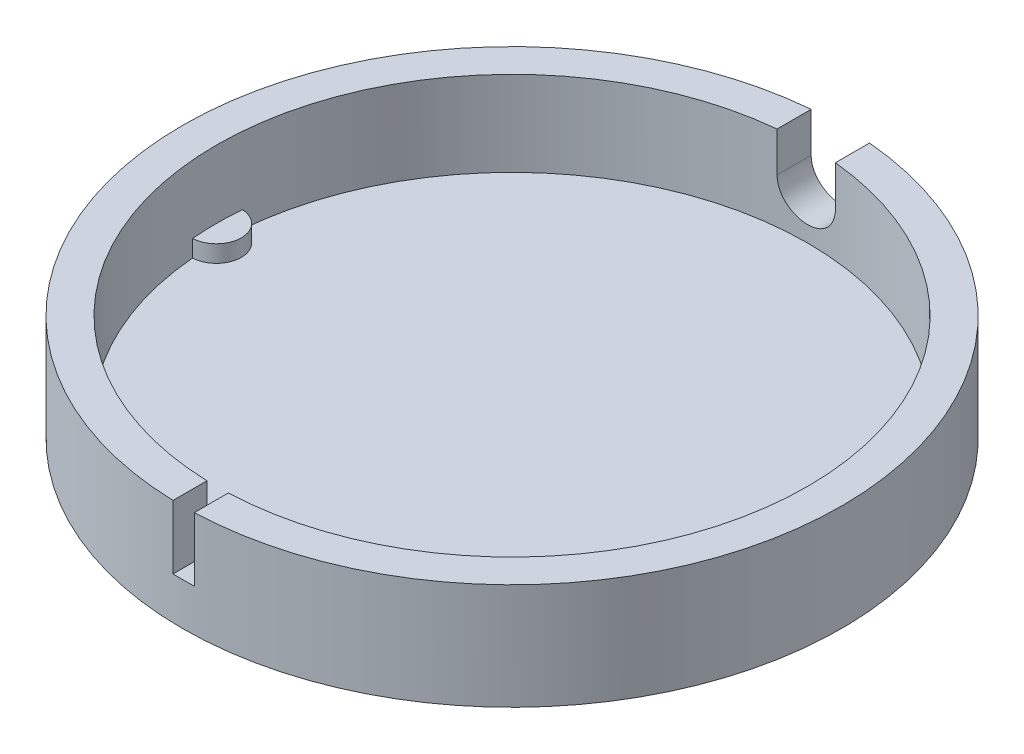
SolidWorks part; units mm, degrees
ref_plane "Front Plane" through (0, 0, 0) normal (0, 0, 1) x (1, 0, 0)
ref_plane "Top Plane" through (0, 0, 0) normal (0, 1, 0) x (1, 0, 0)
ref_plane "Right Plane" through (0, 0, 0) normal (1, 0, 0) x (0, 0, -1)
sketch "Sketch1" plane through (0, 0, 0) normal (0, 1, 0) x (1, 0, 0)
  circle A0 centre (0, 0) radius 31.06
  dimension "D1" = 62.12
extrude "Boss-Extrude1" add sketch "Sketch1" along normal blind 10
sketch "Sketch2" plane through (0, 10, 0) normal (0, 1, 0) x (1, 0, 0)
  circle A0 centre (0, 0) radius 27.86
  circle A1 centre (0, 0) radius 31.06 construction
  circle A2 centre (0, 0) radius 31.06
  dimension "D1" = 3.2
extrude "Cut-Extrude1" cut sketch "Sketch2" against normal blind 8 contours A0 region at (0, 10, 0)
sketch "Sketch3" plane through (0, 2, 0) normal (0, 1, 0) x (1, 0, 0)
  arc A0 (-27.7609, -2.3479) -> (-27.7609, 2.3479) centre (-27.86, 0) ccw
  circle A1 centre (0, 0) radius 27.86 construction
  arc A2 (27.7609, 2.3479) -> (27.7609, -2.3479) centre (27.86, 0) ccw
  arc A3 (27.7609, -2.3479) -> (27.7609, 2.3479) centre (0, 0) ccw
  arc A4 (-27.7609, 2.3479) -> (-27.7609, -2.3479) centre (0, 0) ccw
  dimension "D1" = 4.7
  dimension "D2" = 4.7
extrude "Boss-Extrude2" add sketch "Sketch3" along normal blind 1.6
sketch "Sketch4" plane through (0, 0, 0) normal (0, 0, 1) x (1, 0, 0)
  line L0 (27.7609, 2) -> (-27.7609, 2) construction
  line L1 (27.7609, 2) -> (-27.7609, 2)
  line L2 (0, 0) -> (0, 4.7714)
  line L3 (27.86, 10) -> (-27.86, 10) construction
  line L4 (27.86, 10) -> (-27.86, 10)
  line L5 (-2.75, 6.25) -> (-2.75, 10)
  line L6 (2.75, 6.25) -> (2.75, 10)
  circle A0 centre (0, 6.25) radius 2.75
  dimension "D1" = 5.5
  dimension "D2" = 4.25
extrude "Cut-Extrude2" cut sketch "Sketch4" against normal through all contours A0 L6 L4 L5 | A0 region at (0, 9.0865, 0)
sketch "Sketch5" plane through (0, 0, 0) normal (0, 0, 1) x (1, 0, 0)
  line L0 (27.86, 10) -> (-27.86, 10) construction
  line L1 (1.0982, 3.999) -> (-0.9018, 3.999)
  line L2 (1.0982, 3.999) -> (1.0982, 10)
  line L3 (1.0982, 5.999) -> (-0.9018, 5.999)
  line L4 (-0.9018, 3.999) -> (-0.9018, 10)
  line L5 (1.0982, 3.999) -> (-0.9018, 5.999) construction
  line L6 (1.0982, 5.999) -> (-0.9018, 3.999) construction
  line L7 (1.0982, 10) -> (-0.9018, 10)
  point P0 (0.0982, 4.999)
  dimension "D1" = 2
  dimension "D2" = 2
  dimension "D3" = 5
extrude "Cut-Extrude3" cut sketch "Sketch5" along normal through all contours L2 L7 L4 L1
